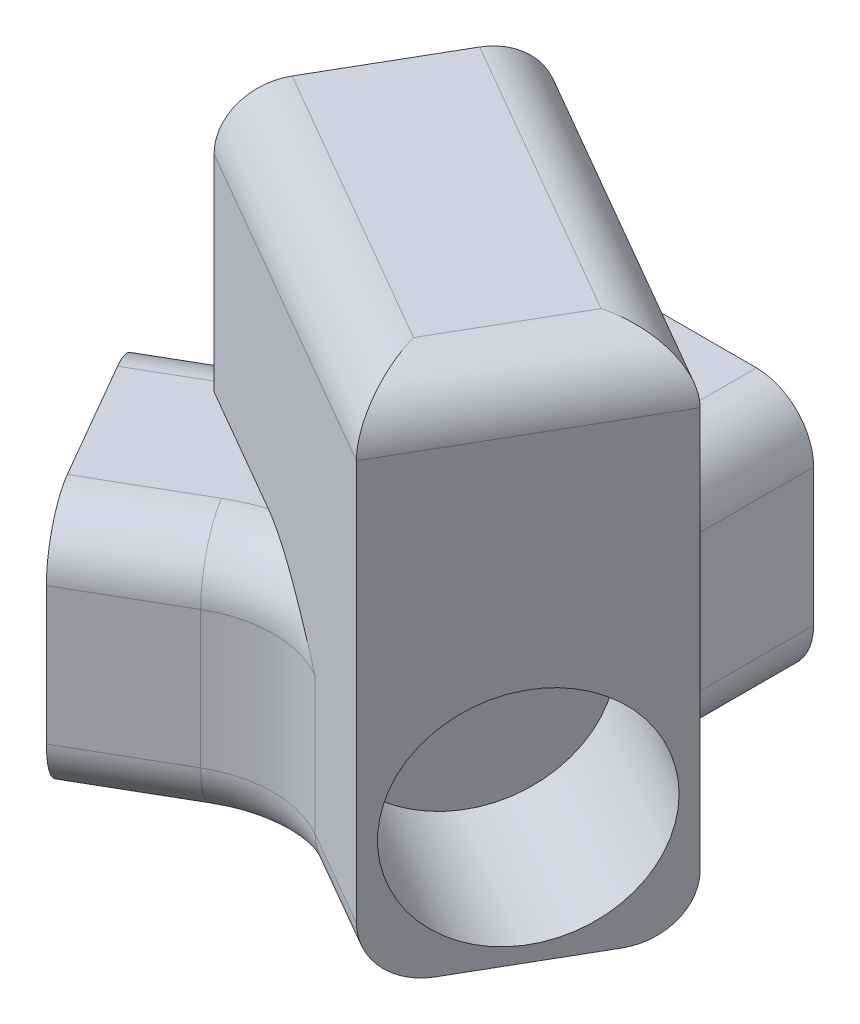
SolidWorks part; units mm, degrees
material "7075-T6 (SN)"
ref_plane "Front" through (0, 0, 0) normal (0, 0, 1) x (1, 0, 0)
ref_plane "Top" through (0, 0, 0) normal (0, 1, 0) x (1, 0, 0)
ref_plane "Right" through (0, 0, 0) normal (1, 0, 0) x (0, 0, -1)
sketch "Sketch1" plane through (0, 0, 0) normal (0, 1, 0) x (1, 0, 0)
  line L0 (-11, 22) -> (11, 22)
  line L1 (11, 22) -> (11, 6.3509)
  line L2 (0, 0) -> (0, 22) construction
  line L3 (-11, 22) -> (-11, 6.3509)
  line L5 (24.5526, -1.4737) -> (13.5526, -20.5263)
  line L6 (13.5526, -20.5263) -> (0, -12.7017)
  line L7 (24.5526, -1.4737) -> (11, 6.3509)
  line L9 (0, 0) -> (19.0526, -11) construction
  line L10 (-13.5526, -20.5263) -> (-24.5526, -1.4737)
  line L11 (-24.5526, -1.4737) -> (-11, 6.3509)
  line L12 (-13.5526, -20.5263) -> (0, -12.7017)
  line L14 (0, 0) -> (-19.0526, -11) construction
  point P19 (0, 0)
  dimension "D1" = 22
  dimension "D3" = 22
  dimension "D2" = 3
extrude "Boss-Extrude1" add sketch "Sketch1" along normal blind 22
sketch "Sketch2" plane through (0, 0, -22) normal (0, 0, -1) x (-1, 0, 0)
  line L0 (0, 22) -> (0, 0) construction
  line L1 (-11, 22) -> (11, 22) construction
  circle A0 centre (0, 11) radius 9.652
  dimension "D1" = 19.304
extrude "Cut-Extrude1" cut sketch "Sketch2" against normal blind 15
ref_axis "Axis1" through (0, 23.1, 0) along (0, -1, 0)
pattern_circular "CirPattern1" count 3 over 360 about axis through (0, 23.1, 0) along (0, -1, 0) of "Cut-Extrude1"
fillet "Fillet2" radius 10 3 edges at (0, 11, 12.7017) (-11, 11, -6.3509) (11, 11, -6.3509)
sketch "Sketch7" plane through (0, 22, 0) normal (0, 1, 0) x (1, 0, 0)
  line L0 (24.5526, -1.4737) -> (-4.8923, 15.5263)
  line L1 (-4.8923, 15.5263) -> (-15.8923, -3.5263)
  line L2 (-15.8923, -3.5263) -> (13.5526, -20.5263)
  line L3 (13.5526, -20.5263) -> (24.5526, -1.4737)
  line L4 (24.5526, -1.4737) -> (16, 3.4641) construction
  line L5 (5, -15.5885) -> (13.5526, -20.5263) construction
  dimension "D1" = 12
extrude "Boss-Extrude3" add sketch "Sketch7" along normal blind 23
sketch "Sketch8" plane through (-10.3923, 0, -6) normal (-0.866, 0, -0.5) x (-0.5, 0, 0.866)
  line L0 (0, 45) -> (0, 22) construction
  line L1 (-11, 45) -> (11, 45) construction
  line L2 (-11, 22) -> (11, 22) construction
  line L3 (5, 22) -> (13.5526, 22) construction
  circle A0 centre (0, 33) radius 9.652
  dimension "D1" = 19.304
  dimension "D2" = 11
extrude "Cut-Extrude5" cut sketch "Sketch8" against normal offset from surface (31 mm away) 3 up to face at (23.8786, 11, 2.6411)
fillet "Fillet3" radius 5 18 edges at (9.2763, 0, 18.0574) (0, 0, 14.2487) (-20.2763, 0, -0.9952) (-12.3397, 0, -7.1244) (20.2763, 0, -0.9952) (12.3397, 0, -7.1244) (-11, 22, -17.0622) (-1.1699, 45, 12.0263) (19.0526, 45, 11) (9.8301, 45, -7.0263) (-9.2763, 0, 18.0574) (-11, 0, -17.0622) (11, 0, -17.0622) (11, 22, -17.0622) (-20.2763, 22, -0.9952) (-9.2763, 22, 18.0574)
